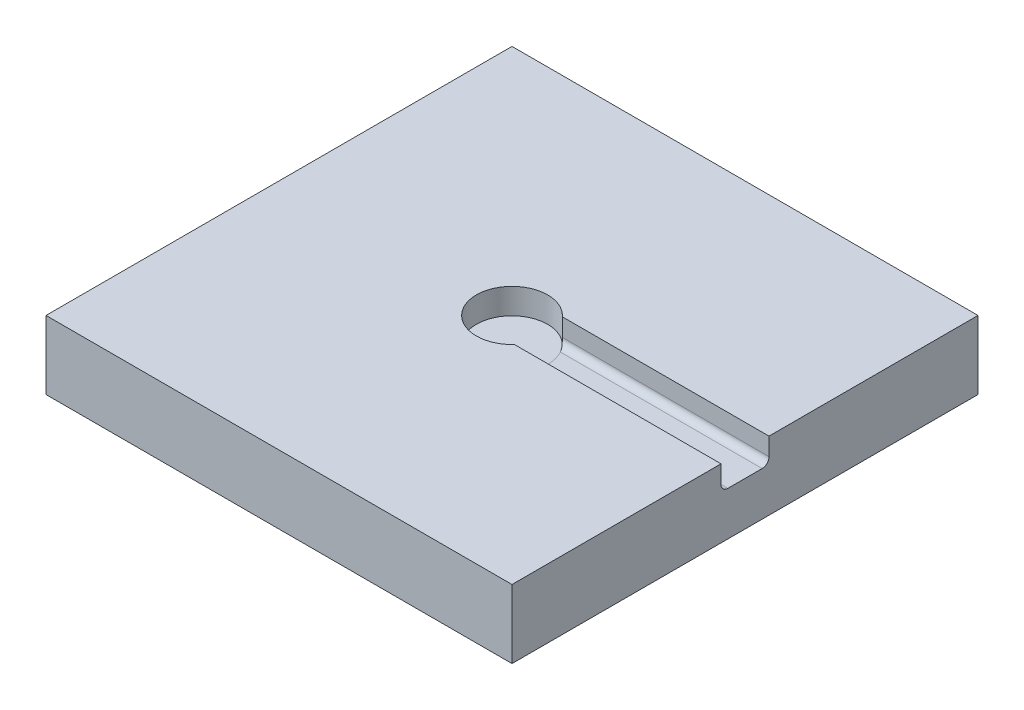
SolidWorks part; units mm, degrees
ref_plane "Front Plane" through (0, 0, 0) normal (0, 0, 1) x (1, 0, 0)
ref_plane "Top Plane" through (0, 0, 0) normal (0, 1, 0) x (1, 0, 0)
ref_plane "Right Plane" through (0, 0, 0) normal (1, 0, 0) x (0, 0, -1)
sketch "Sketch1" plane through (0, 0, 0) normal (0, 1, 0) x (1, 0, 0)
  line L1 (170, 170) -> (-170, 170)
  line L2 (170, 170) -> (170, -170)
  line L3 (170, -170) -> (-170, -170)
  line L4 (-170, 170) -> (-170, -170)
  line L5 (170, 170) -> (-170, -170) construction
  line L6 (170, -170) -> (-170, 170) construction
  point P0 (0, 0)
  dimension "D1" = 340
  dimension "D2" = 340
extrude "base" add sketch "Sketch1" along normal blind 50
sketch "Sketch2" plane through (0, 50, 0) normal (0, 1, 0) x (1, 0, 0)
  circle A0 centre (0, 0) radius 26
  dimension "D1" = 52
extrude "load cell cut" cut sketch "Sketch2" against normal blind 18.6 contours A0
sketch "Sketch3" plane through (170, 0, 0) normal (1, 0, 0) x (0, 0, -1)
  line L1 (-17.5, 32) -> (17.5, 32)
  line L2 (-17.5, 32) -> (-17.5, 50)
  line L3 (-17.5, 50) -> (17.5, 50)
  line L4 (17.5, 32) -> (17.5, 50)
  line L5 (-170, 50) -> (170, 50) construction
  line L6 (-170, 0) -> (170, 0) construction
  point P6 (0, 32)
  point P10 (0, 0)
  dimension "D1" = 18
  dimension "D2" = 35
extrude "wire cut" cut sketch "Sketch3" against normal blind 170
fillet "wire cut fillet" radius 5 2 edges at (94.6144, 32, 17.5) (94.6144, 32, -17.5)
